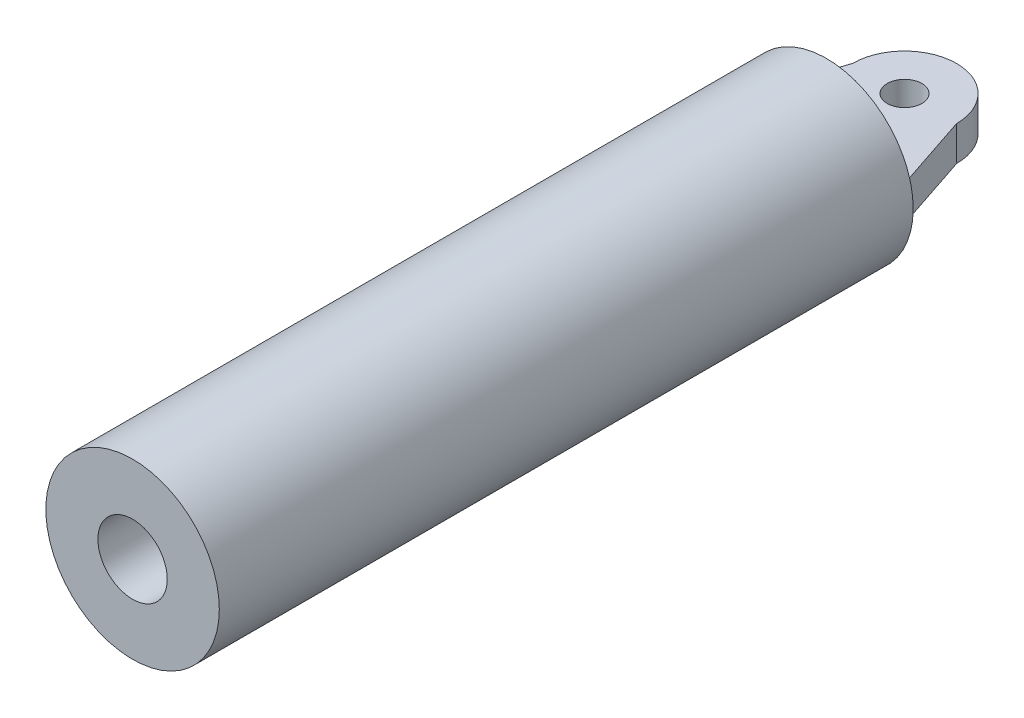
SolidWorks part; units mm, degrees
ref_plane "Front Plane" through (0, 0, 0) normal (0, 0, 1) x (1, 0, 0)
ref_plane "Top Plane" through (0, 0, 0) normal (0, 1, 0) x (1, 0, 0)
ref_plane "Right Plane" through (0, 0, 0) normal (1, 0, 0) x (0, 0, -1)
sketch "Sketch1" plane through (0, 0, 0) normal (0, 0, 1) x (1, 0, 0)
  circle A0 centre (0, 0) radius 50
  dimension "D1" = 100
extrude "Boss-Extrude1" add sketch "Sketch1" along normal blind 400
sketch "Sketch3" plane through (0, 0, 0) normal (0, 1, 0) x (1, 0, 0)
  line L0 (50, 0) -> (-50, 0) construction
  line L1 (-45, 0) -> (45, 0)
  line L2 (-45, 0) -> (-30, 45)
  line L3 (-30, 45) -> (-30.0741, 45.3303)
  line L4 (30, 45) -> (45, 0)
  line L5 (45, 0) -> (44.7988, -0.1795)
  circle A0 centre (0, 45) radius 10
  arc A1 (-30, 45) -> (30, 45) centre (0, 45) cw
  point P5 (-45, 0)
  point P9 (45, 0)
  dimension "D1" = 20
  dimension "D3" = 45
  dimension "D5" = 30
  dimension "D2" = 45
  dimension "D4" = 45
extrude "Boss-Extrude2" add sketch "Sketch3" along normal mid plane 20 contours A1 L2 L1 L4 A0 region at (0, 0, -30.9204)
shell "Shell1" thickness 30 removed face at (50, 0, 400)
